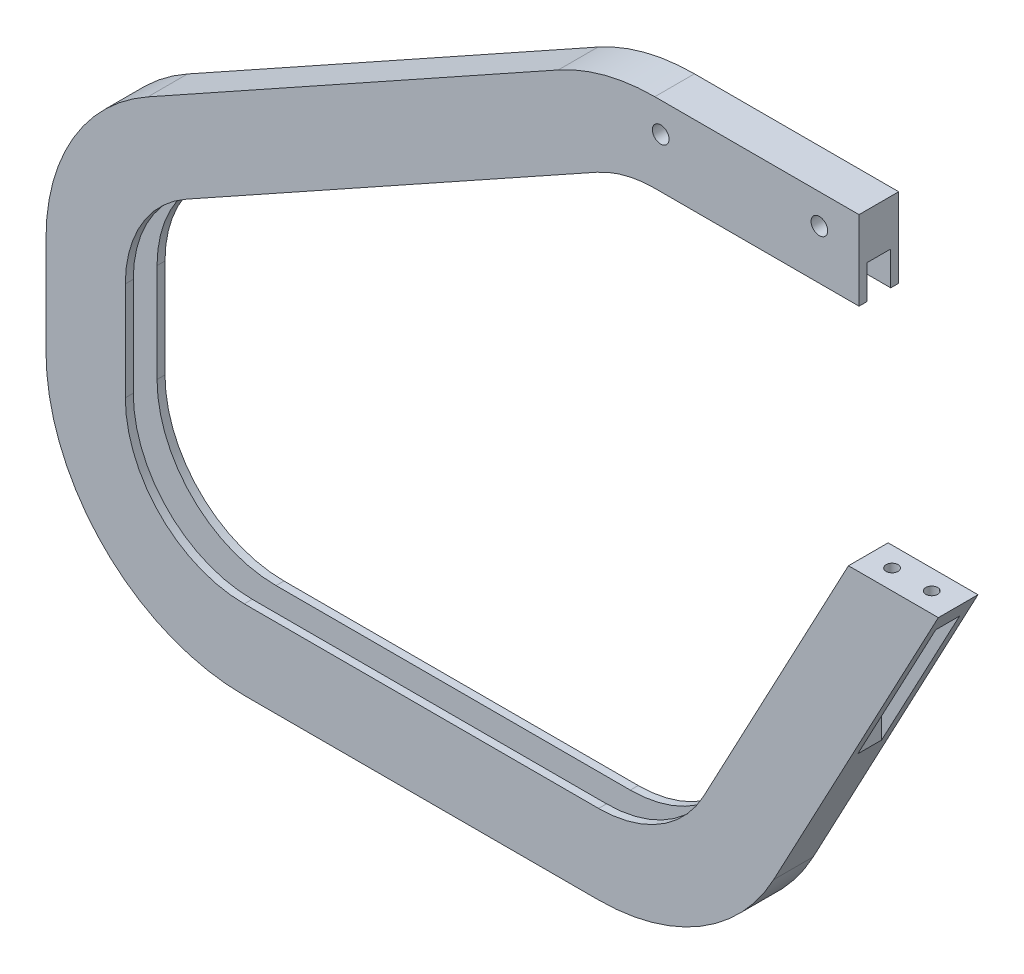
SolidWorks part; units mm, degrees
ref_plane "前视基准面" through (0, 0, 0) normal (0, 0, 1) x (1, 0, 0)
ref_plane "上视基准面" through (0, 0, 0) normal (0, 1, 0) x (1, 0, 0)
ref_plane "右视基准面" through (0, 0, 0) normal (1, 0, 0) x (0, 0, -1)
sketch "草图1" plane through (0, 0, 0) normal (0, 0, 1) x (1, 0, 0)
  line L0 (-137.9301, -127.3336) -> (-137.9301, 127.3336) construction
  line L1 (-176.9301, -127.3336) -> (-98.9301, -127.3336) construction
  line L2 (-98.9301, 127.3336) -> (-176.9301, 127.3336) construction
  line L3 (-225.1052, -135.4999) -> (-262.9301, -135.4999) construction
  line L5 (-232.9301, -77.4999) -> (-232.9301, -57.5)
  line L6 (-232.9301, -57.5) -> (-284.4239, -57.5)
  line L10 (-232.9301, -77.4999) -> (-284.4237, -77.4999)
  line L15 (-417.9301, -165.1328) -> (-417.9301, -190)
  line L16 (-387.9301, -240) -> (-298.6019, -240)
  line L18 (-387.9301, -220) -> (-298.6019, -220)
  line L22 (-212.9301, -135.4999) -> (-235.5893, -135.4999)
  line L24 (-345.3931, 0) -> (69.533, 0) construction
  line L25 (-345.3931, -39) -> (-345.3931, 39) construction
  line L26 (69.533, 39) -> (69.533, -39) construction
  line L27 (-212.9301, -135.4999) -> (-235.5893, -135.4999)
  line L28 (-308.7477, -63.8153) -> (-412.2539, -121.4481)
  line L29 (-299.018, -81.2891) -> (-402.5244, -138.922)
  line L30 (-235.5893, -135.4999) -> (-272.1226, -204.1014)
  line L31 (-337.9301, -77.4999) -> (-230.9301, -77.4999) construction
  line L32 (-254.4698, -213.5023) -> (-212.9301, -135.4999)
  line L33 (-437.9301, -165.1328) -> (-437.9301, -190)
  circle A0 centre (-242.9301, -65) radius 2.1 construction
  circle A1 centre (-282.9301, -65) radius 2.1 construction
  circle A2 centre (-242.9301, -65) radius 2.1
  circle A3 centre (-282.9301, -65) radius 2.1
  arc A4 (-298.6019, -220) -> (-272.1226, -204.1014) centre (-298.6019, -190) ccw
  arc A5 (-387.9301, -220) -> (-417.9301, -190) centre (-387.9301, -190) cw
  arc A6 (-417.9301, -165.1328) -> (-402.5244, -138.922) centre (-387.9301, -165.1328) cw
  arc A7 (-284.4237, -77.4999) -> (-299.018, -81.2891) centre (-284.4237, -107.4999) ccw
  arc A8 (-308.7477, -63.8153) -> (-284.4239, -57.5) centre (-284.4239, -107.5) cw
  arc A9 (-412.2539, -121.4481) -> (-437.9301, -165.1328) centre (-387.9301, -165.1328) ccw
  arc A10 (-437.9301, -190) -> (-387.9301, -240) centre (-387.9301, -190) ccw
  arc A11 (-298.6019, -240) -> (-254.4698, -213.5023) centre (-298.6019, -190) ccw
  point P39 (-280.5893, -220)
  point P47 (-417.9301, -147.4999)
  dimension "D1" = 20
  dimension "D2" = 10
  dimension "D3" = 7.5
  dimension "D11" = 30
  dimension "D13" = 50
  dimension "D14" = 50
  dimension "D15" = 50
  dimension "D16" = 50
  dimension "D4" = 20
  dimension "D5" = 240
  dimension "D6" = 20
  dimension "D7" = 300
  dimension "D8" = 20
  dimension "D9" = 20
  dimension "D10" = 70
  dimension "D12" = 45
extrude "凸台-拉伸1" add sketch "草图1" along normal blind 10 contours L16 A11 L32 L22 L30 A4 L18 A5 L15 A6 L29 A7 L10 L5 L6 A8 L28 A9 L33 A10 A2 A3 region at (-258.6769, -74.6028, 0)
ref_plane "基准面2" through (0, 0, 5) normal (0, 0, 1) x (1, 0, 0)
sketch "草图4" plane through (0, 0, 5) normal (0, 0, 1) x (1, 0, 0)
  line L0 (-232.9301, -69) -> (-296.0976, -69)
  line L1 (-317.9891, -74.6838) -> (-409.8215, -125.8166)
  line L2 (-432.9301, -165.1328) -> (-432.9301, -189.7411)
  line L3 (-387.9301, -234.7411) -> (-299.096, -234.7411)
  line L4 (-259.3771, -210.8931) -> (-240.2397, -174.9575)
  line L5 (-230.5893, -140.4999) -> (-235.2397, -140.4999)
  line L6 (-235.2397, -140.4999) -> (-235.2397, -167.1528)
  line L7 (-240.2397, -174.9575) -> (-240.2397, -144.2324)
  line L9 (-230.5893, -140.4999) -> (-215.5928, -140.4999)
  line L10 (-235.2397, -140.4999) -> (-235.2397, -177.3925)
  line L12 (-387.9301, -240) -> (-298.6019, -240)
  line L13 (-254.4698, -213.5023) -> (-212.9301, -135.4999)
  line L14 (-212.9301, -135.4999) -> (-235.5893, -135.4999)
  line L15 (-235.5893, -135.4999) -> (-272.1226, -204.1014)
  line L16 (-298.6019, -220) -> (-387.9301, -220)
  line L17 (-417.9301, -190) -> (-417.9301, -165.1328)
  line L18 (-402.5244, -138.922) -> (-299.018, -81.2891)
  line L19 (-284.4237, -77.4999) -> (-232.9301, -77.4999)
  line L20 (-232.9301, -77.4999) -> (-232.9301, -57.5)
  line L21 (-232.9301, -57.5) -> (-284.4239, -57.5)
  line L22 (-308.7477, -63.8153) -> (-412.2539, -121.4481)
  line L23 (-437.9301, -165.1328) -> (-437.9301, -190)
  line L27 (-240.2397, -144.2324) -> (-272.1226, -204.1014)
  line L28 (-298.6019, -220) -> (-387.9301, -220)
  line L29 (-417.9301, -190) -> (-417.9301, -165.1328)
  line L30 (-402.5244, -138.922) -> (-299.018, -81.2891)
  line L31 (-284.4237, -77.4999) -> (-232.9301, -77.4999)
  line L32 (-232.9301, -77.4999) -> (-232.9301, -69)
  line L36 (-215.5928, -140.4999) -> (-235.2397, -177.3925)
  line L37 (-254.4698, -213.5023) -> (-212.9301, -135.4999) construction
  line L38 (-212.9301, -135.4999) -> (-235.5893, -135.4999) construction
  circle A0 centre (-242.9301, -65) radius 2.1 construction
  arc A1 (-299.096, -234.7411) -> (-259.3771, -210.8931) centre (-299.096, -189.7411) ccw
  arc A2 (-432.9301, -189.7411) -> (-387.9301, -234.7411) centre (-387.9301, -189.7411) ccw
  arc A3 (-409.8215, -125.8166) -> (-432.9301, -165.1328) centre (-387.9301, -165.1328) ccw
  arc A4 (-296.0976, -69) -> (-317.9891, -74.6838) centre (-296.0976, -114) ccw
  arc A8 (-298.6019, -240) -> (-254.4698, -213.5023) centre (-298.6019, -190) ccw
  arc A9 (-298.6019, -220) -> (-272.1226, -204.1014) centre (-298.6019, -190) ccw
  arc A10 (-417.9301, -190) -> (-387.9301, -220) centre (-387.9301, -190) ccw
  arc A11 (-402.5244, -138.922) -> (-417.9301, -165.1328) centre (-387.9301, -165.1328) ccw
  arc A12 (-284.4237, -77.4999) -> (-299.018, -81.2891) centre (-284.4237, -107.4999) ccw
  arc A13 (-284.4239, -57.5) -> (-308.7477, -63.8153) centre (-284.4239, -107.5) ccw
  arc A14 (-412.2539, -121.4481) -> (-437.9301, -165.1328) centre (-387.9301, -165.1328) ccw
  arc A15 (-437.9301, -190) -> (-387.9301, -240) centre (-387.9301, -190) ccw
  arc A17 (-298.6019, -220) -> (-272.1226, -204.1014) centre (-298.6019, -190) ccw
  arc A18 (-417.9301, -190) -> (-387.9301, -220) centre (-387.9301, -190) ccw
  arc A19 (-402.5244, -138.922) -> (-417.9301, -165.1328) centre (-387.9301, -165.1328) ccw
  arc A20 (-284.4237, -77.4999) -> (-299.018, -81.2891) centre (-284.4237, -107.4999) ccw
  dimension "D7" = 45
  dimension "D2" = 5
  dimension "D3" = 5
  dimension "D6" = 4
  dimension "D1" = 0
extrude "切除-拉伸1" cut sketch "草图4" against normal blind 3 and the other way blind 3 contours L9 L36 L10 L5 | L27 A17 L28 A18 L29 A19 L30 A20 L31 L32 L0 A4 L1 A3 L2 A2 L3 A1 L4 L7
sketch "草图5" plane through (0, -140.4999, 0) normal (0, -1, 0) x (1, 0, 0)
  line L0 (100.375, 5) -> (-100.375, 5) construction
  line L1 (-215.5928, 8) -> (-215.5928, 2) construction
  circle A0 centre (-229.5928, 5) radius 1.5
  circle A1 centre (-219.5928, 5) radius 1.5
  dimension "D1" = 3
  dimension "D2" = 3
  dimension "D3" = 4
  dimension "D4" = 10
extrude "切除-拉伸2" cut sketch "草图5" against normal blind 5
